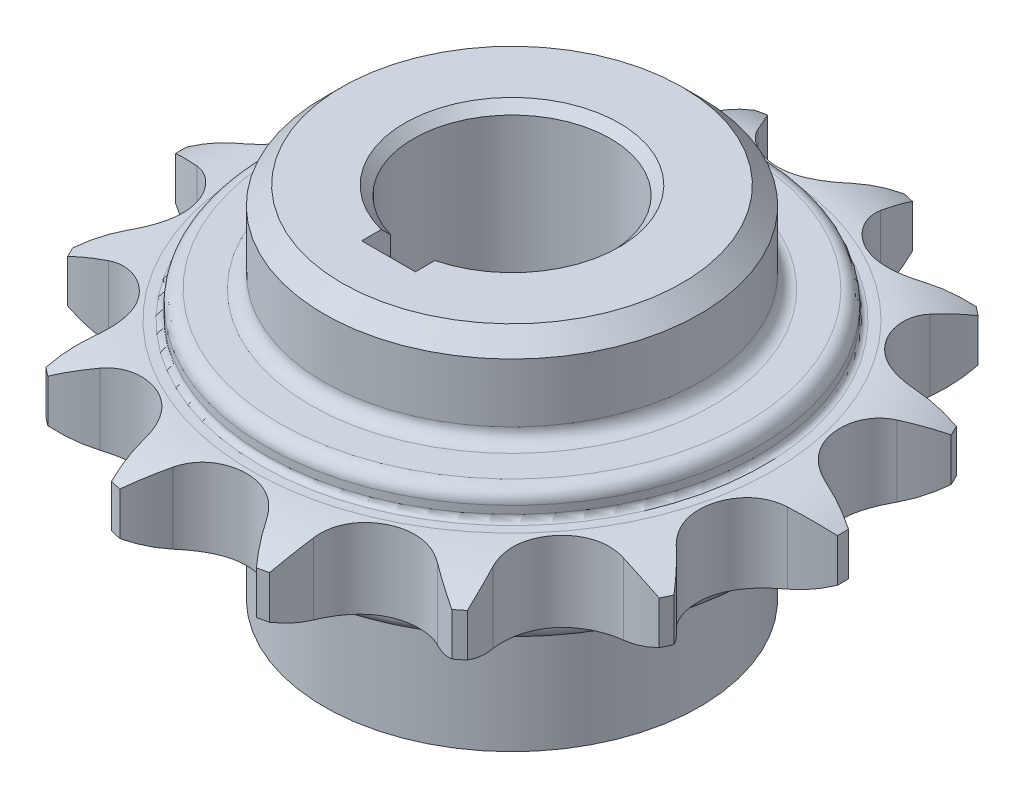
SolidWorks part; units mm, degrees
material "AISI 1045 钢，冷拔"
ref_plane "前视基准面" through (0, 0, 0) normal (0, 0, 1) x (1, 0, 0)
ref_plane "上视基准面" through (0, 0, 0) normal (0, 1, 0) x (1, 0, 0)
ref_plane "右视基准面" through (0, 0, 0) normal (1, 0, 0) x (0, 0, -1)
sketch "草图1" plane through (0, 0, 0) normal (0, 1, 0) x (1, 0, 0)
  line L0 (0, 0) -> (0, 51.7486) construction
  line L1 (0, 0) -> (25.3679, 52.6769) construction
  line L2 (0, 35.6709) -> (32.0589, 17.1616) construction
  line L3 (15.477, 32.1383) -> (-15.3885, 29.8253) construction
  line L4 (0, 29.6709) -> (0, 0)
  line L5 (0, 0) -> (12.8737, 26.7325)
  circle A0 centre (0, 0) radius 35.6709 construction
  arc A1 (0, 29.6709) -> (5.1962, 32.6708) centre (0, 35.6709) ccw
  arc A2 (9.4938, 31.6899) -> (12.8737, 26.7325) centre (15.477, 32.1383) ccw
  arc A3 (8.8341, 35.9299) -> (7.6301, 36.2047) centre (0, 0) ccw
  arc A4 (7.6301, 36.2047) -> (5.1962, 32.6708) centre (28.5788, 19.1708) ccw
  arc A5 (9.4938, 31.6899) -> (8.8341, 35.9299) centre (-17.4307, 29.6722) ccw
  point P150 (0, 0)
  dimension "D1" = 71.3417
  dimension "D3" = 12
  dimension "D4" = 12
  dimension "D5" = 74
  dimension "D8" = 54
  dimension "D9" = 54
  dimension "D2" = 25.714
  dimension "D6" = 60
  dimension "D7" = 60
extrude "凸台-拉伸1" add sketch "草图1" along normal blind 8.93
pattern_circular "阵列(圆周)1" count 14 over 360 about axis through (0, 8.93, 0) along (0, 1, 0) of "凸台-拉伸1"
sketch "草图2" plane through (0, 0, 0) normal (0, 0, 1) x (1, 0, 0)
  line L0 (36.9948, 4.465) -> (-36.9948, 4.465) construction
  line L1 (36.9948, 8.93) -> (36.9948, 0) construction
  line L2 (-36.9948, 8.93) -> (-36.9948, 0) construction
  line L3 (39.2107, 6.8663) -> (27.425, 6.8662) construction
  line L4 (39.2107, 2.0638) -> (27.425, 2.0637) construction
  line L5 (33.008, 0) -> (36.9948, 0) construction
  line L6 (36.9948, 8.93) -> (33.008, 8.93) construction
  line L7 (28.7828, 8.93) -> (21.8886, 8.93) construction
  line L8 (36.9948, 8.93) -> (36.9948, 0) construction
  line L9 (36.9948, 8.93) -> (29.1677, 8.93)
  line L10 (21.8886, 0) -> (28.7828, 0) construction
  line L13 (36.9948, 0) -> (29.1677, 0)
  line L14 (36.9948, 6.8663) -> (36.9948, 2.0637)
  line L15 (36.9948, 8.93) -> (43.7467, 8.93)
  line L16 (43.7467, 8.93) -> (43.7467, 0)
  line L17 (43.7467, 0) -> (36.9948, 0)
  line L18 (0, 0) -> (0, 52.4922) construction
  arc A0 (36.9948, 6.8663) -> (29.1677, 8.93) centre (29.1677, -6.945) ccw
  arc A1 (29.1677, 0) -> (36.9948, 2.0637) centre (29.1677, 15.875) ccw
  point P22 (36.9948, 6.8663)
  point P25 (36.9948, 2.0637)
  dimension "D3" = 31.75
  dimension "D4" = 31.75
  dimension "D1" = 2.0638
  dimension "D2" = 2.0638
revolve "切除-旋转1" cut sketch "草图2" angle 360 about L18
sketch "草图4" plane through (0, 0, 0) normal (0, -1, 0) x (1, 0, 0)
  circle A0 centre (0, 0) radius 27.5
  dimension "D1" = 55
extrude "凸台-拉伸3" add sketch "草图4" along normal blind 3
sketch "草图3" plane through (0, 8.93, 0) normal (0, 1, 0) x (1, 0, 0)
  circle A0 centre (0, 0) radius 27.5
  dimension "D1" = 55
extrude "凸台-拉伸2" add sketch "草图3" along normal blind 3
sketch "草图5" plane through (0, 11.93, 0) normal (0, 1, 0) x (1, 0, 0)
  circle A0 centre (0, 0) radius 21
  dimension "D1" = 42
extrude "凸台-拉伸4" add sketch "草图5" along normal offset from surface (10.07 mm away) 25 up to face at (0, -3, -27.5)
fillet "圆角1" radius 0.635 2 edges at (0, 8.93, 27.5) (0, 0, 27.5)
fillet "圆角2" radius 1.5 3 edges at (0, 11.93, 21) (0, 11.93, 27.5) (0, -3, -27.5)
chamfer "倒角1" distance 2 angle 45 1 edges at (0, 22, -21)
sketch "草图8" plane through (0, -3, 0) normal (0, -1, 0) x (1, 0, 0)
  circle A0 centre (0, 0) radius 21
  dimension "D1" = 42
extrude "凸台-拉伸5" add sketch "草图8" along normal offset from surface (15 mm away) 40 up to face at (0, 22, -19)
sketch "草图6" plane through (0, 22, 0) normal (0, 1, 0) x (1, 0, 0)
  circle A0 centre (0, 0) radius 11
  dimension "D1" = 22
extrude "切除-拉伸3" cut sketch "草图6" against normal blind 40
chamfer "倒角2" distance 1 angle 45 2 edges at (0, 22, 11) (0, -18, 11)
sketch "草图7" plane through (0, -3, 0) normal (0, -1, 0) x (1, 0, 0)
  line L0 (0, 0) -> (0, 52.6933) construction
  line L1 (-3, 10.583) -> (-3, 13.8)
  line L2 (3, 10.583) -> (3, 13.8)
  line L3 (-3, 13.8) -> (3, 13.8)
  line L5 (-3, 0) -> (-3, 52.6933) construction
  line L6 (3, 0) -> (3, 52.6933) construction
  circle A0 centre (0, 0) radius 11 construction
  arc A1 (3, 10.583) -> (-3, 10.583) centre (0, 0) ccw
  dimension "D1" = 3
  dimension "D3" = 13.8
  dimension "D2" = 3
extrude "切除-拉伸4" cut sketch "草图7" against normal up to next
extrude "切除-拉伸5" cut sketch "草图7<3>" along normal up to surface (15 mm away) up to face at (0, -18, -12)
sketch "草图7<3>" plane through (0, -3, 0) normal (0, -1, 0) x (1, 0, 0) same geometry as "草图7"
